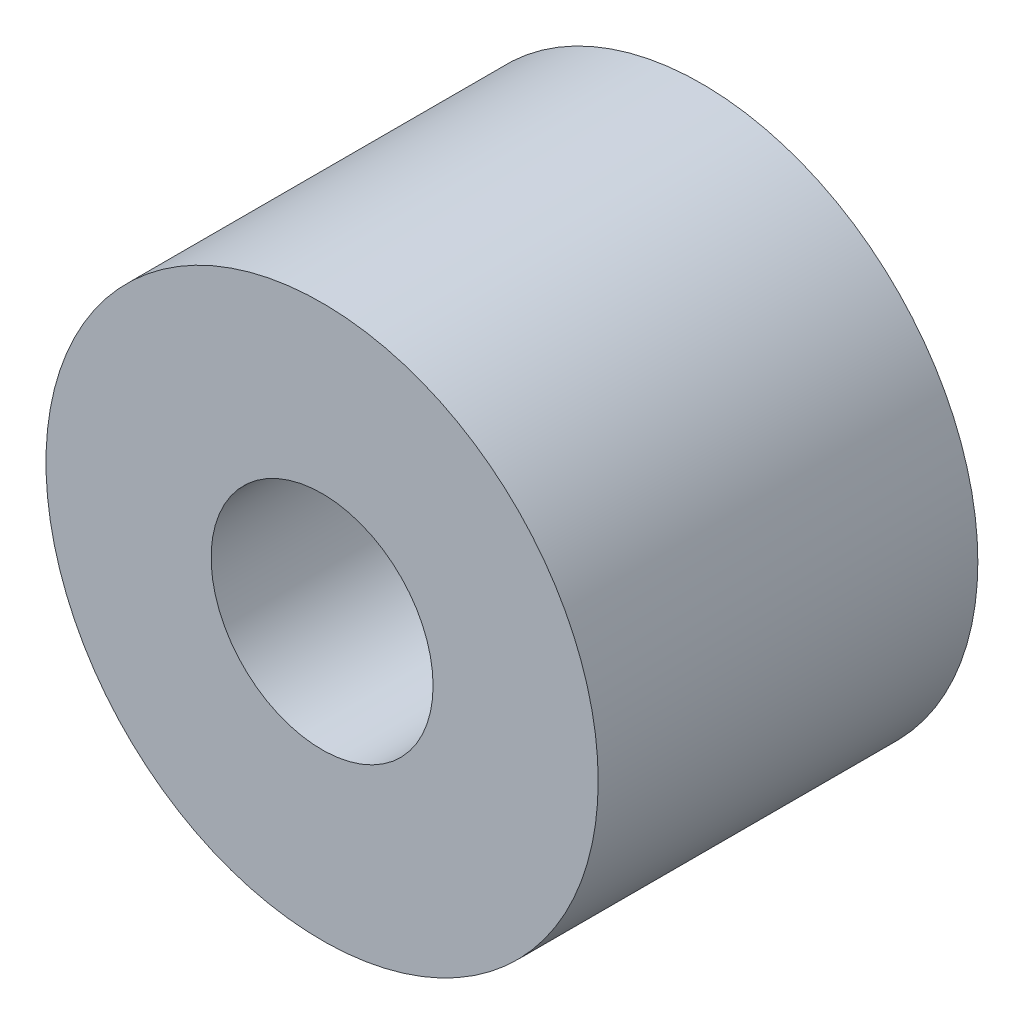
SolidWorks part; units mm, degrees
ref_plane "Front Plane" through (0, 0, 0) normal (0, 0, 1) x (1, 0, 0)
ref_plane "Top Plane" through (0, 0, 0) normal (0, 1, 0) x (1, 0, 0)
ref_plane "Right Plane" through (0, 0, 0) normal (1, 0, 0) x (0, 0, -1)
sketch "Sketch1" plane through (0, 0, 0) normal (0, 0, 1) x (1, 0, 0)
  circle A0 centre (0, 0) radius 6.35
  dimension "D1" = 12.7
extrude "Boss-Extrude1" add sketch "Sketch1" along normal mid plane 8.7312
sketch "Sketch2" plane through (0, 0, 4.3656) normal (0, 0, 1) x (1, 0, 0)
  point P0 (0, 0)
hole_wizard "Tap Drill for 1/4-20 Tap1" positions "Sketch2" profile "Sketch3" hole size "1/4-20" standard "ANSI Inch" end condition through all
sketch "Sketch3" plane through (0, 0, 4.3656) normal (1, 0, 0) x (0, -1, 0)
  line L0 (0, 0) -> (0, 8.7312)
  line L1 (0, 8.7312) -> (2.5527, 8.7312)
  line L2 (2.5527, 8.7312) -> (2.5527, 0)
  line L5 (2.5527, 0) -> (0, 0)
  line L11 (0, -6.35) -> (0, 107.95) construction
  dimension "Thru Hole Dia." = 5.1054
  dimension "Thru Hole Depth" = 8.7312
cosmetic thread "Cosmetic Thread1" parameters "D2"=6.1054
equation "\"AIRFRAME_OD\"= 3.091in"
equation "\"AIRFRAME_ID\"= 3.00in"
equation "\"FLAT_T\"= 0.125in"
equation "\"NOSE_EXP_L\"= 3.5in"
equation "\"NOSE_SHOULDER_L\"= 5in"
equation "\"MAIN_L\"= 26in"
equation "\"RECO_COUP_L\"= 6in"
equation "\"RECO_SWITCH_L\"= 1.5in"
equation "\"DROGUE_L\"= 14in"
equation "\"ATS_FORE_COUP_L\"= 4in"
equation "\"ATS_AFT_COUP_L\"= 2.5in"
equation "\"LOWER_L\"= 16in"
equation "\"FIN_N\"= 4"
equation "\"CR_AFT_X\"= 0.5in"
equation "\"CR_FORE_X\"= 6in"
